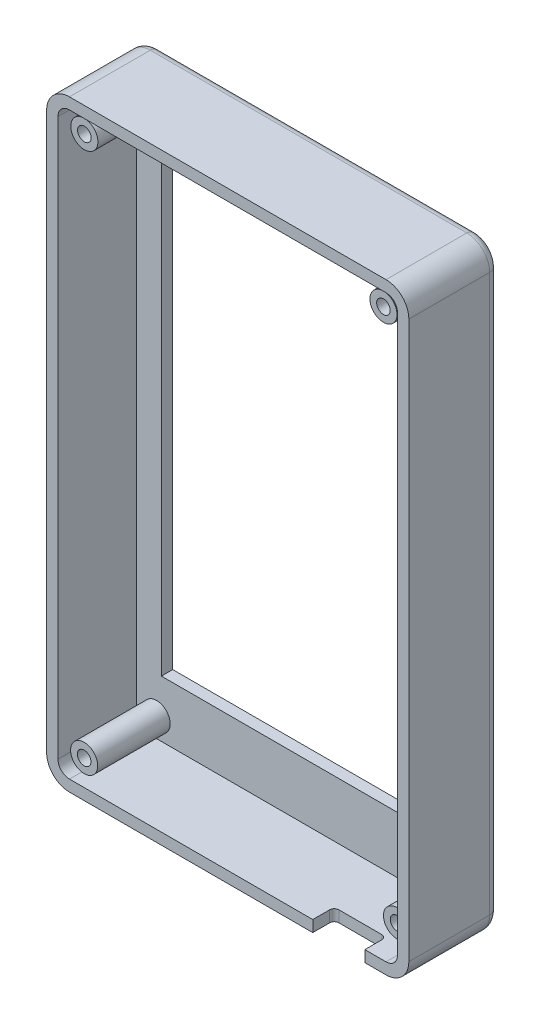
SolidWorks part; units mm, degrees
material "Plastique personnalisé"
ref_plane "Plan de face" through (0, 0, 0) normal (0, 0, 1) x (1, 0, 0)
ref_plane "Plan de dessus" through (0, 0, 0) normal (0, 1, 0) x (1, 0, 0)
ref_plane "Plan de droite" through (0, 0, 0) normal (1, 0, 0) x (0, 0, -1)
sketch "Esquisse1" plane through (0, 0, 0) normal (0, 0, 1) x (1, 0, 0)
  line L1 (-34.96, -64) -> (34.96, -64)
  line L2 (-37.5, -61.46) -> (-37.5, 61.46)
  line L3 (-34.96, 64) -> (34.96, 64)
  line L4 (37.5, -61.46) -> (37.5, 61.46)
  line L5 (-37.5, -64) -> (37.5, 64) construction
  line L6 (-37.5, 64) -> (37.5, -64) construction
  arc A0 (34.96, -64) -> (37.5, -61.46) centre (34.96, -61.46) ccw
  arc A1 (-34.96, -64) -> (-37.5, -61.46) centre (-34.96, -61.46) cw
  arc A2 (-37.5, 61.46) -> (-34.96, 64) centre (-34.96, 61.46) cw
  arc A3 (34.96, 64) -> (37.5, 61.46) centre (34.96, 61.46) cw
  point P0 (0, 0)
  dimension "D3" = 2.54
  dimension "D1" = 128
  dimension "D2" = 75
extrude "Boss.-Extru.1" add sketch "Esquisse1" along normal blind 17.35
shell "Coque1" thickness 2.5 removed face at (0, 0, 17.35) outward yes
fillet "Congé1" radius 2 8 edges at (40, 0, -2.5) (38.5238, -65.0238, -2.5) (0, -66.5, -2.5) (-38.5238, -65.0238, -2.5) (-40, 0, -2.5) (-38.5238, 65.0238, -2.5) (0, 66.5, -2.5) (38.5238, 65.0238, -2.5)
sketch "Esquisse3" plane through (0, 0, 0) normal (0, 0, 1) x (1, 0, 0)
  circle A0 centre (-33.02, 59.69) radius 1.5
  circle A1 centre (-33.02, 59.69) radius 3
  circle A2 centre (33.0465, 59.69) radius 1.5
  circle A3 centre (33.0465, 59.69) radius 3
  circle A4 centre (-33.06, -59.69) radius 3
  circle A5 centre (-33.06, -59.69) radius 1.5
  circle A6 centre (33.0465, -59.759) radius 3
  circle A7 centre (33.0465, -59.759) radius 1.5
  dimension "D1" = 3
  dimension "D2" = 3
extrude "Boss.-Extru.2" add sketch "Esquisse3" along normal blind 17
sketch "Esquisse5" plane through (0, 0, 0) normal (0, 0, 1) x (1, 0, 0)
  circle A0 centre (-33.02, 59.69) radius 1.5
  circle A1 centre (33.0465, 59.69) radius 1.5
  circle A2 centre (33.0465, -59.759) radius 1.5
  circle A3 centre (-33.06, -59.69) radius 1.5
extrude "Enlèv. mat.-Extru.3" cut sketch "Esquisse5" against normal through all both and the other way through all
sketch "Esquisse6" plane through (0, 0, -2.5) normal (0, 0, -1) x (-1, 0, 0)
  line L0 (0, -66.5) -> (0, -51.5) construction
  line L2 (34.96, -66.5) -> (-34.96, -66.5) construction
  line L4 (-40, -51.5) -> (40, -51.5) construction
  line L6 (0, 66.5) -> (0, 57) construction
  line L7 (-34.96, 66.5) -> (34.96, 66.5) construction
  line L8 (-40, -61.46) -> (-40, 61.46) construction
  line L9 (40, 61.46) -> (40, -61.46) construction
  line L10 (-40, 57) -> (40, 57) construction
  line L11 (-40, 0) -> (-28, 0) construction
  line L12 (40, 0) -> (32, 0) construction
  line L13 (32, 0) -> (32, -51.5) construction
  line L14 (-28, 0) -> (-28, 57) construction
  line L16 (-28, 57) -> (32, 57)
  line L17 (-28, 57) -> (-28, -51.5)
  line L18 (-28, -51.5) -> (32, -51.5)
  line L19 (32, 57) -> (32, -51.5)
  dimension "D1" = 15
  dimension "D2" = 12
  dimension "D3" = 8
extrude "Enlèv. mat.-Extru.4" cut sketch "Esquisse6" against normal blind 10
sketch "Esquisse7" plane through (0, 0, 0) normal (0, 0, 1) x (1, 0, 0)
  line L0 (-32, 56.8687) -> (28, -51.5) construction
sketch "Esquisse8" plane through (0, -66.5, 0) normal (0, -1, 0) x (-1, 0, 0)
  line L0 (34.96, -17.35) -> (-34.96, -17.35) construction
  line L1 (-29.5029, -17.35) -> (-19.5514, -17.35)
  line L2 (-29.5029, -17.35) -> (-29.5029, -14.35)
  line L3 (-28.5029, -13.35) -> (-20.5514, -13.35)
  line L4 (-19.5514, -17.35) -> (-19.5514, -14.35)
  arc A0 (-20.5514, -13.35) -> (-19.5514, -14.35) centre (-20.5514, -14.35) cw
  arc A1 (-29.5029, -14.35) -> (-28.5029, -13.35) centre (-28.5029, -14.35) cw
  point P10 (-29.5029, -13.35)
  dimension "D2" = 1
  dimension "D1" = 4
extrude "Enlèv. mat.-Extru.5" cut sketch "Esquisse8" against normal blind 10
fillet "Congé2" radius 0.2 2 edges at (29.5029, -65.25, 17.35) (19.5514, -65.25, 17.35)
sketch "Esquisse9" plane through (0, -66.5, 0) normal (0, -1, 0) x (1, 0, 0)
  line L1 (30.2818, 19.1) -> (18.7818, 19.1)
  line L2 (30.2818, 19.1) -> (30.2818, 13.6)
  line L3 (29.2818, 12.6) -> (19.7818, 12.6)
  line L4 (18.7818, 19.1) -> (18.7818, 13.6)
  line L5 (30.2818, 19.1) -> (18.7818, 12.6) construction
  line L6 (30.2818, 12.6) -> (18.7818, 19.1) construction
  arc A0 (30.2818, 13.6) -> (29.2818, 12.6) centre (29.2818, 13.6) cw
  arc A1 (19.7818, 12.6) -> (18.7818, 13.6) centre (19.7818, 13.6) cw
  point P0 (24.5318, 15.85)
  dimension "D1" = 1
extrude "Enlèv. mat.-Extru.6" cut sketch "Esquisse9" against normal blind 10
sketch "Esquisse10" plane through (0, 0, 17) normal (0, 0, 1) x (1, 0, 0)
  circle A0 centre (33.0465, -59.759) radius 3
extrude "Enlèv. mat.-Extru.8" cut sketch "Esquisse10" against normal blind 4
sketch "Esquisse11" plane through (0, 0, 17) normal (0, 0, 1) x (1, 0, 0)
  circle A0 centre (-33.02, 59.69) radius 3
  circle A1 centre (33.0465, 59.69) radius 3
  circle A2 centre (-33.06, -59.69) radius 3
extrude "Enlèv. mat.-Extru.9" cut sketch "Esquisse11" against normal blind 1
